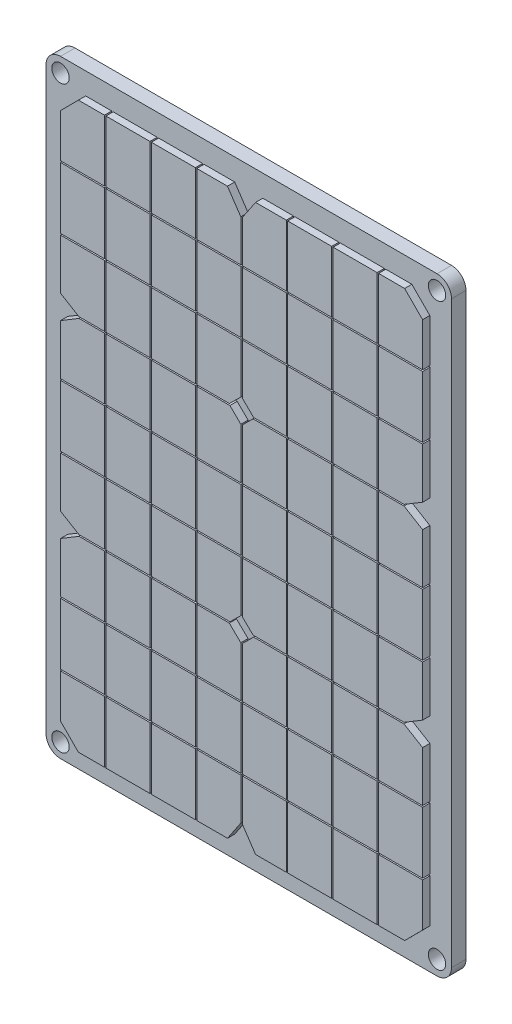
SolidWorks part; units mm, degrees
ref_plane "Front Plane" through (0, 0, 0) normal (0, 0, 1) x (1, 0, 0)
ref_plane "Top Plane" through (0, 0, 0) normal (0, 1, 0) x (1, 0, 0)
ref_plane "Right Plane" through (0, 0, 0) normal (1, 0, 0) x (0, 0, -1)
sketch "Sketch1" plane through (0, 0, 0) normal (0, 0, 1) x (1, 0, 0)
  line L1 (-140, 210) -> (140, 210)
  line L2 (-140, 210) -> (-140, -210)
  line L3 (-140, -210) -> (140, -210)
  line L4 (140, 210) -> (140, -210)
  line L5 (-140, 210) -> (140, -210) construction
  line L6 (-140, -210) -> (140, 210) construction
  point P0 (0, 0)
  dimension "D1" = 420
  dimension "D2" = 280
extrude "Boss-Extrude1" add sketch "Sketch1" along normal blind 10
sketch "Sketch3" plane through (0, 0, 10) normal (0, 0, 1) x (1, 0, 0)
  line L0 (-125, 195) -> (-94.625, 195)
  line L1 (-94.625, 195) -> (-94.625, 152.56)
  line L2 (-94.625, 152.56) -> (-125, 152.56)
  line L3 (-125, 152.56) -> (-125, 195)
  line L4 (-140, 210) -> (-140, -210) construction
  line L5 (140, 210) -> (-140, 210) construction
  dimension "D1" = 30.375
  dimension "D2" = 42.44
  dimension "D3" = 15
  dimension "D4" = 15
extrude "Boss-Extrude2" add sketch "Sketch3" along normal blind 5
pattern_linear "LPattern1" count 8 spacing 31.38 along (1, 0, 0) of "Boss-Extrude2"
pattern_linear "LPattern2" count 9 spacing 43.44 along (0, -1, 0) of "LPattern1"
fillet "Fillet1" radius 10 4 edges at (-140, -210, 5) (-140, 210, 5) (140, 210, 5) (140, -210, 5)
sketch "Sketch4" plane through (0, 0, 10) normal (0, 0, 1) x (1, 0, 0)
  circle A0 centre (-130, -200) radius 6
  arc A1 (-140, -200) -> (-130, -210) centre (-130, -200) ccw construction
  dimension "D1" = 12
extrude "Cut-Extrude1" cut sketch "Sketch4" against normal through all
mirror "Mirror2" about plane through (0, 0, 0) normal (1, 0, 0) of "Cut-Extrude1"
mirror "Mirror4" about plane through (0, 0, 0) normal (0, 1, 0) of "Mirror2", "Cut-Extrude1"
sketch "Sketch6" plane through (0, 0, 15) normal (0, 0, 1) x (1, 0, 0)
  line L0 (0, 73.9275) -> (8.6889, 65.3455)
  line L4 (8.6889, 65.3455) -> (-0.0311, 56.7952)
  line L5 (-0.0311, 56.7952) -> (-8.72, 65.3772)
  line L6 (-8.72, 65.3772) -> (0, 73.9275)
extrude "Cut-Extrude2" cut sketch "Sketch6" against normal blind 5
mirror "Mirror5" about plane through (0, 0, 0) normal (0, 1, 0) of "Cut-Extrude2"
sketch "Sketch7" plane through (0, 0, 15) normal (0, 0, 1) x (1, 0, 0)
  line L0 (-9.7131, 195) -> (0, 180.5696)
  line L1 (-0.485, 195) -> (-30.86, 195) construction
  line L3 (0, 180.5696) -> (9.7131, 195)
  line L4 (30.895, 195) -> (0.52, 195) construction
  line L5 (9.7131, 195) -> (-9.7131, 195)
extrude "Cut-Extrude3" cut sketch "Sketch7" against normal blind 5
mirror "Mirror6" about plane through (0, 0, 0) normal (0, 1, 0) of "Cut-Extrude3"
sketch "Sketch8" plane through (0, 0, 15) normal (0, 0, 1) x (1, 0, 0)
  line L0 (125.035, 73.3709) -> (111.3903, 65.1609)
  line L1 (125.035, 65.68) -> (125.035, 108.12) construction
  line L2 (111.3903, 65.1609) -> (125.035, 56.951)
  line L3 (125.035, 22.24) -> (125.035, 64.68) construction
  line L4 (125.035, 56.951) -> (125.035, 73.3709)
extrude "Cut-Extrude4" cut sketch "Sketch8" against normal blind 5
mirror "Mirror7" about plane through (0, 0, 0) normal (1, 0, 0) of "Cut-Extrude4"
mirror "Mirror8" about plane through (0, 0, 0) normal (0, 1, 0) of "Cut-Extrude4", "Mirror7"
sketch "Sketch9" plane through (0, 0, 15) normal (0, 0, 1) x (1, 0, 0)
  line L0 (-126.7919, 180.7587) -> (-112.625, 195)
  line L2 (-94.625, 195) -> (-125, 195) construction
  line L3 (-112.625, 195) -> (-126.7919, 195)
  line L4 (-126.7919, 195) -> (-126.7919, 180.7587)
extrude "Cut-Extrude5" cut sketch "Sketch9" against normal blind 5
mirror "Mirror10" about plane through (0, 0, 0) normal (1, 0, 0) of "Cut-Extrude5"
mirror "Mirror11" about plane through (0, 0, 0) normal (0, 1, 0) of "Mirror10", "Cut-Extrude5"
